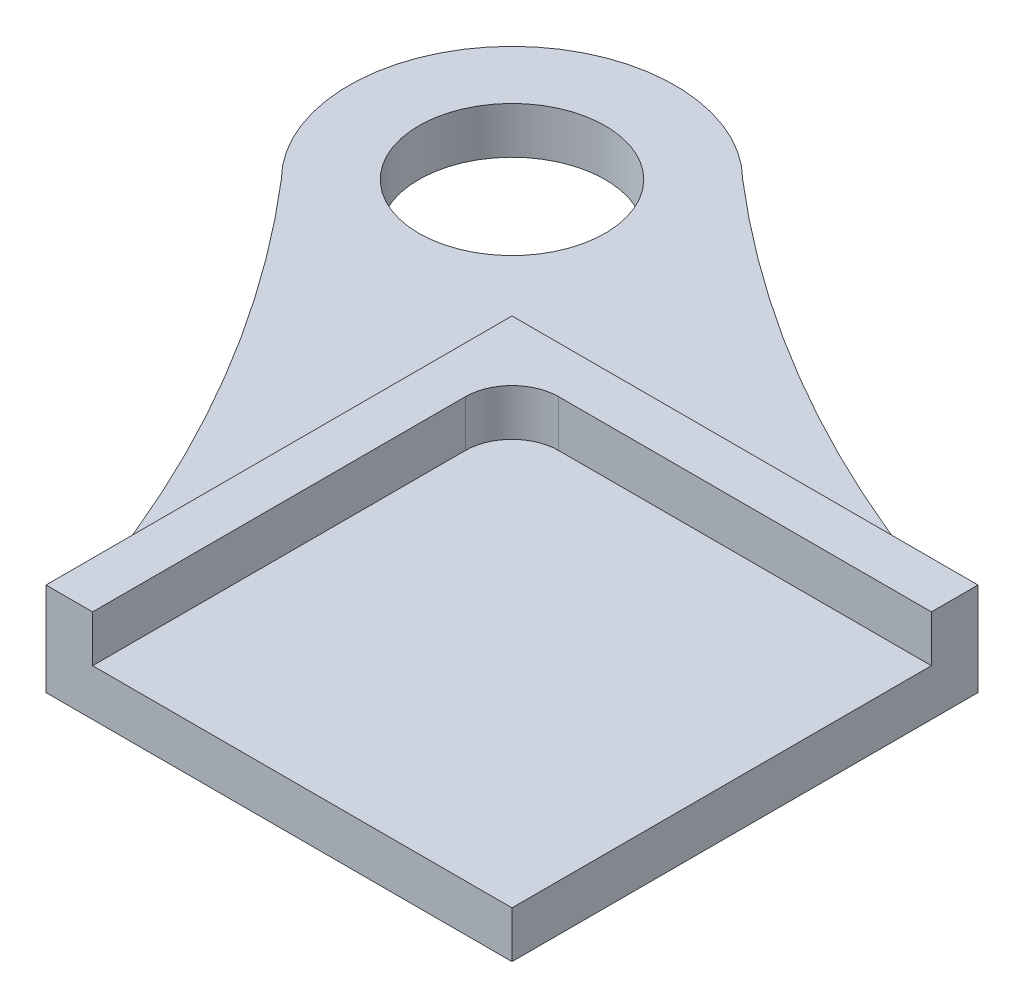
SolidWorks part; units mm, degrees
ref_plane "Front Plane" through (0, 0, 0) normal (0, 0, 1) x (1, 0, 0)
ref_plane "Top Plane" through (0, 0, 0) normal (0, 1, 0) x (1, 0, 0)
ref_plane "Right Plane" through (0, 0, 0) normal (1, 0, 0) x (0, 0, -1)
sketch "Sketch1" plane through (0, 0, 0) normal (0, 1, 0) x (1, 0, 0)
  line L0 (-10, 10) -> (-17.0711, 17.0711) construction
  line L1 (-10, -10) -> (10, -10)
  line L2 (-10, -10) -> (-10, 10)
  line L3 (-10, 10) -> (10, 10)
  line L4 (10, -10) -> (10, 10)
  line L5 (-10, -10) -> (10, 10) construction
  line L6 (-10, 10) -> (10, -10) construction
  line L7 (-17.0711, 17.0711) -> (-22.0206, 22.0211) construction
  line L13 (-12.1211, 22.0206) -> (-22.0211, 12.1216) construction
  circle A0 centre (-17.0711, 17.0711) radius 4
  circle A1 centre (-17.0711, 17.0711) radius 7
  arc A2 (-10, -10) -> (-22.0211, 12.1216) centre (-67.5562, -26.9496) ccw
  arc A3 (10, 10) -> (-12.1211, 22.0206) centre (26.9495, 67.5562) cw
  point P0 (0, 0)
  dimension "D5" = 8
  dimension "D6" = 14
  dimension "D10" = 60
  dimension "D9" = 60
  dimension "D1" = 20
  dimension "D2" = 20
  dimension "D3" = 45
  dimension "D4" = 10
  dimension "D7" = 4.95
  dimension "D8" = 4.95
extrude "Boss-Extrude2" add sketch "Sketch1" against normal blind 2 contours A1 A3 A2 A0 | L3 A3 A1 A2 L2 | L1 L4 L3 L2 region at (0, 0, 0) region at (-14.4393, 0, -1.9146) region at (-21.8806, 0, -21.8811)
sketch "Sketch2" plane through (0, 0, 0) normal (0, 1, 0) x (1, 0, 0)
  line L0 (-8, -10) -> (-8, 10) construction
  line L2 (10, -10) -> (-10, -10) construction
  line L4 (10, -10) -> (10, 10) construction
  line L5 (10, 10) -> (-10, 10)
  line L17 (-10, -10) -> (-10, 10)
  line L18 (10, 8) -> (-10, 8) construction
  line L19 (-8, 6) -> (-8, -10)
  line L20 (-6, 8) -> (10, 8)
  arc A1 (-6, 8) -> (-8, 6) centre (-6, 6) ccw
  point P12 (-8, 8)
  line M28 (10, -10) -> (10, 10)
  line M32 (-10, -10) -> (10, -10)
  dimension "D3" = 2
  dimension "D5" = 2
  dimension "D1" = 20
  dimension "D2" = 20
  dimension "D4" = 2
extrude "Boss-Extrude3" add sketch "Sketch2" along normal blind 2 contours A1 L20 L5 L17 L19 M28 M32
